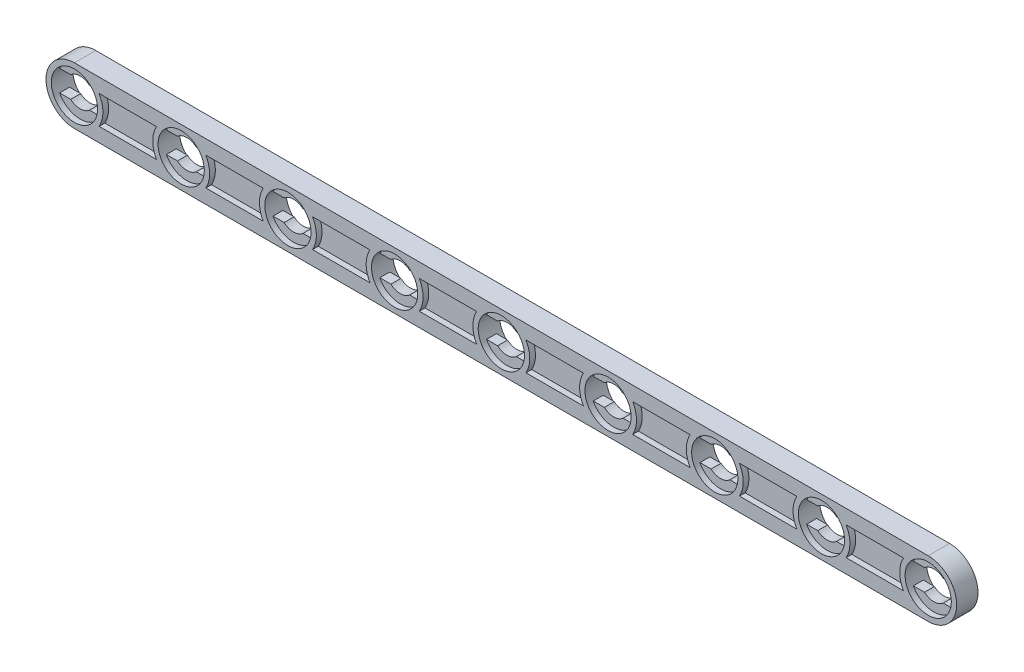
SolidWorks part; units mm, degrees
ref_plane "前视基准面" through (0, 0, 0) normal (0, 0, 1) x (1, 0, 0)
ref_plane "上视基准面" through (0, 0, 0) normal (0, 1, 0) x (1, 0, 0)
ref_plane "右视基准面" through (0, 0, 0) normal (1, 0, 0) x (0, 0, -1)
sketch "草图1" plane through (0, 0, 0) normal (0, 0, 1) x (1, 0, 0)
  line L1 (0, 4) -> (120, 4)
  line L3 (0, -4) -> (120, -4)
  arc A0 (0, 4) -> (0, -4) centre (0, 0) ccw
  arc A1 (120, -4) -> (120, 4) centre (120, 0) ccw
  dimension "D1" = 4
  dimension "D2" = 120
  dimension "D3" = 120
extrude "凸台-拉伸1" add sketch "草图1" against normal blind 3
sketch "草图2" plane through (0, 0, 0) normal (0, 0, 1) x (1, 0, 0)
  line L0 (1.3229, -1.5) -> (2.8831, -1.5)
  line L1 (-2.8831, -1.5) -> (-1.3229, -1.5)
  line L2 (1.3229, 1.5) -> (2.8831, 1.5)
  line L3 (-2.8831, 1.5) -> (-1.3229, 1.5)
  arc A0 (1.3229, 1.5) -> (-1.3229, 1.5) centre (0, 0) ccw
  arc A1 (-2.8831, 1.5) -> (-2.8831, -1.5) centre (0, 0) ccw
  arc A3 (2.8831, -1.5) -> (2.8831, 1.5) centre (0, 0) ccw
  arc A4 (-1.3229, -1.5) -> (1.3229, -1.5) centre (0, 0) ccw
extrude "切除-拉伸1" cut sketch "草图2" against normal up to next
sketch "草图3" plane through (0, 0, 0) normal (0, 0, 1) x (1, 0, 0)
  circle A1 centre (0, 0) radius 3.25
extrude "切除-拉伸2" cut sketch "草图3" against normal blind 0.8
extrude "切除-拉伸3" cut sketch "草图3<2>" along normal blind 0.8 from offset 3 offset against normal yes
sketch "草图3<2>" plane through (0, 0, 0) normal (0, 0, 1) x (1, 0, 0) same geometry as "草图3"
sketch "草图4" plane through (0, 0, 0) normal (0, 0, 1) x (1, 0, 0)
  line L1 (3.4641, 2) -> (11.5359, 2)
  line L3 (3.4641, -2) -> (11.5359, -2)
  arc A0 (11.5359, 2) -> (11.5359, -2) centre (15, 0) ccw
  arc A2 (3.4641, -2) -> (3.4641, 2) centre (0, 0) ccw
extrude "切除-拉伸4" cut sketch "草图4" against normal blind 0.8
sketch "草图5" plane through (0, 0, -3) normal (0, 0, -1) x (-1, 0, 0)
  line L1 (-4, -2) -> (-11, -2)
  line L2 (-4, -2) -> (-4, 2)
  line L3 (-4, 2) -> (-11, 2)
  line L4 (-11, -2) -> (-11, 2)
extrude "切除-拉伸6" cut sketch "草图5" against normal blind 0.8
pattern_linear "阵列(线性)1" count 9 spacing 15 along (1, 0, 0) of "切除-拉伸1", "切除-拉伸2", "切除-拉伸3"
pattern_linear "阵列(线性)2" count 8 spacing 15 along (1, 0, 0) of "切除-拉伸4", "切除-拉伸6"
